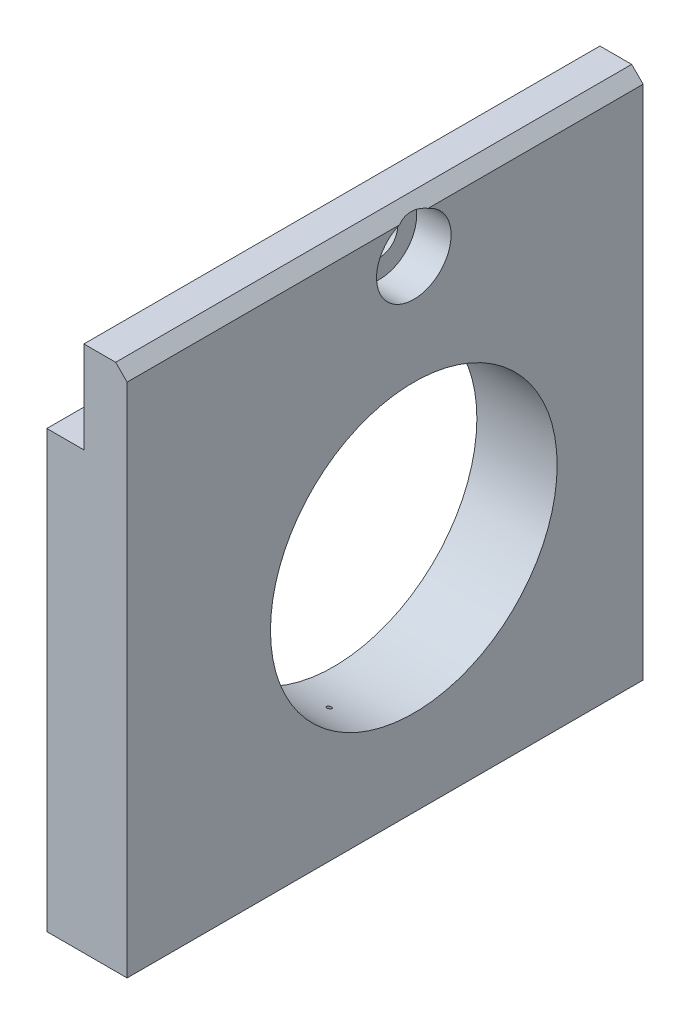
SolidWorks part; units mm, degrees
material "6061-T6 (SS)"
ref_plane "Front" through (0, 0, 0) normal (0, 0, 1) x (1, 0, 0)
ref_plane "Top" through (0, 0, 0) normal (0, 1, 0) x (1, 0, 0)
ref_plane "Right" through (0, 0, 0) normal (1, 0, 0) x (0, 0, -1)
sketch "Sketch1" plane through (0, 0, 0) normal (0, 0, 1) x (1, 0, 0)
  line L2 (3.23, 30.3627) -> (3.23, 22.3627)
  line L3 (3.23, 22.3627) -> (0, 22.3627)
  line L4 (0, 22.3627) -> (0, -15.6373)
  line L5 (0, -15.6373) -> (7, -15.6373)
  line L6 (7, -15.6373) -> (7, 30.3627)
  line L8 (3.23, 30.3627) -> (7, 30.3627)
  dimension "D1" = 8
  dimension "D2" = 7
  dimension "D3" = 38
  dimension "D4" = 3.77
extrude "Boss-Extrude1" add sketch "Sketch1" along normal blind 45
hole_wizard "CBORE for M3 SHCS1" positions "Sketch2" profile "Sketch3" counterbore size "M3" standard "ANSI Metric" end condition through all
sketch "Sketch2" plane through (7, 0, 0) normal (1, 0, 0) x (0, 0, -1)
  line L1 (0, -15.6373) -> (0, 30.3627) construction
  line L2 (-45, 22.3627) -> (0, 22.3627) construction
  point P0 (-20, 26.3627)
  dimension "D1" = 4
  dimension "D2" = 20
sketch "Sketch3" plane through (7, 26.3627, 20) normal (0, 1, 0) x (0, 0, -1)
  line L0 (0, 0) -> (0, 7)
  line L1 (0, 7) -> (1.6, 7)
  line L3 (1.6, 7) -> (1.6, 3)
  line L4 (1.6, 3) -> (3.25, 3)
  line L5 (3.25, 3) -> (3.25, 0)
  line L7 (3.25, 0) -> (0, 0)
  line L11 (0, -6.35) -> (0, 107.95) construction
  dimension "Thru Hole Dia." = 3.2
  dimension "Thru Hole Depth" = 7
  dimension "C'Bore Dia." = 6.5
  dimension "C'Bore Depth" = 3
hole_wizard "Ø25.0 (25) Diameter Hole1" positions "Sketch4" profile "Sketch5" hole size "Ø25.0" standard "ANSI Metric" end condition up to next
sketch "Sketch4" plane through (7, 0, 0) normal (1, 0, 0) x (0, 0, -1)
  line L1 (-45, -15.6373) -> (0, -15.6373) construction
  line L2 (-45, -15.6373) -> (-45, 30.3627) construction
  point P0 (-20, 4.3627)
  dimension "D1" = 20
  dimension "D2" = 25
sketch "Sketch5" plane through (7, 4.3627, 20) normal (0, 1, 0) x (0, 0, -1)
  line L0 (0, 0) -> (0, 7)
  line L1 (0, 7) -> (12.5, 7)
  line L2 (12.5, 7) -> (12.5, 0)
  line L5 (12.5, 0) -> (0, 0)
  line L11 (0, -6.35) -> (0, 107.95) construction
  dimension "Thru Hole Dia." = 25
  dimension "Thru Hole Depth" = 7
chamfer "Chamfer1" distance 1 angle 45 1 edges at (7, 30.3627, 22.5)
hole_wizard "M3x0.5 Tapped Hole1" positions "Sketch6" profile "Sketch7" tap size "M3x0.5" standard "ANSI Metric"
sketch "Sketch6" plane through (0, -15.6373, 0) normal (0, -1, 0) x (-1, 0, 0)
  line L0 (0, -45) -> (0, 0) construction
  line L1 (0, -45) -> (-7, -45) construction
  point P0 (-3.5, -24)
  dimension "D1" = 3.5
  dimension "D2" = 21
sketch "Sketch7" plane through (3.5, -15.6373, 24) normal (1, 0, 0) x (0, 0, -1)
  line L0 (0, 0) -> (0, 8.2511)
  line L1 (0, 8.2511) -> (1.25, 7.5)
  line L2 (1.25, 7.5) -> (1.25, 0)
  line L5 (1.25, 0) -> (0, 0)
  line L10 (0, 8.2511) -> (-1.25, 7.5) construction
  line L11 (0, -6.35) -> (0, 107.95) construction
  dimension "Tap Drill Dia." = 2.5
  dimension "Tap Drill Depth" = 7.5
  dimension "Drill Angle" = 118
cosmetic thread "Hole Thread1" parameters "D1"=6, "D2"=3
hole_wizard "Ø3.0mm Dowel Hole1" positions "Sketch8" profile "Sketch9" hole size "Ø3.0" standard "ANSI Metric"
sketch "Sketch8" plane through (0, -15.6373, 0) normal (0, -1, 0) x (-1, 0, 0)
  line L0 (0, -45) -> (0, 0) construction
  line L1 (0, -45) -> (-7, -45) construction
  line L2 (0, 0) -> (-7, 0) construction
  point P0 (-3.5, -38)
  point P2 (-3.5, -7)
  dimension "D1" = 3.5
  dimension "D2" = 7
  dimension "D3" = 7
sketch "Sketch9" plane through (3.5, -15.6373, 38) normal (1, 0, 0) x (0, 0, -1)
  line L0 (0, 0) -> (0, 8.4013)
  line L1 (0, 8.4013) -> (1.5, 7.5)
  line L2 (1.5, 7.5) -> (1.5, 0)
  line L5 (1.5, 0) -> (0, 0)
  line L10 (0, 8.4013) -> (-1.5, 7.5) construction
  line L11 (0, -6.35) -> (0, 107.95) construction
  dimension "Hole Dia." = 3
  dimension "Hole Depth" = 7.5
  dimension "Drill Angle" = 118
